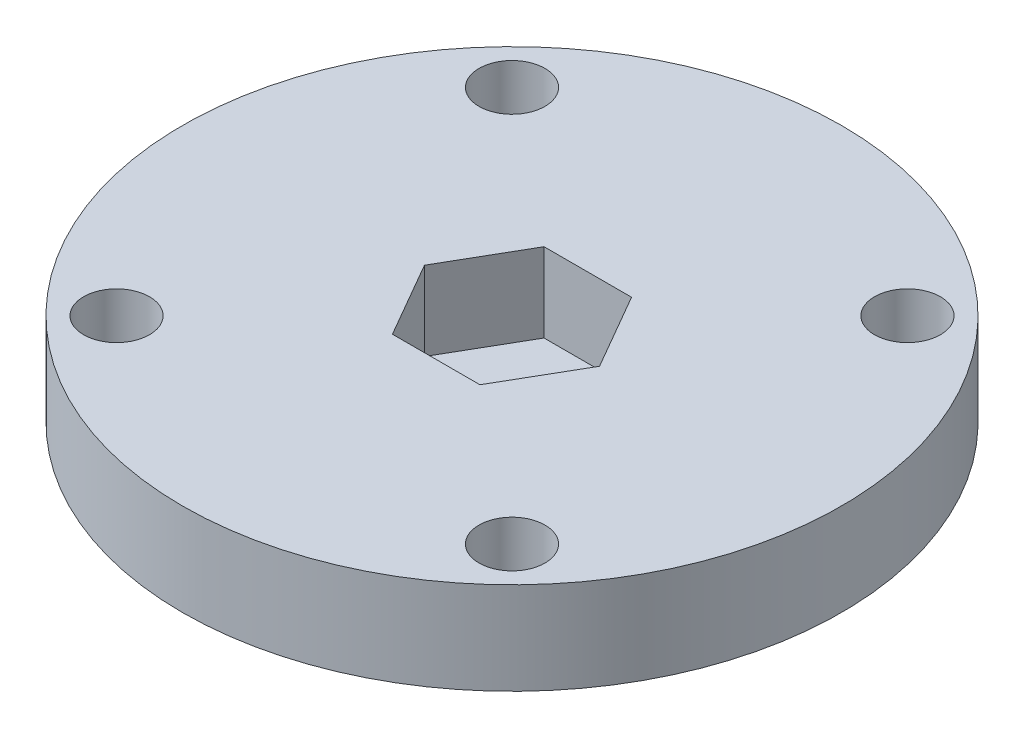
SolidWorks part; units mm, degrees
ref_plane "Front Plane" through (0, 0, 0) normal (0, 0, 1) x (1, 0, 0)
ref_plane "Top Plane" through (0, 0, 0) normal (0, 1, 0) x (1, 0, 0)
ref_plane "Right Plane" through (0, 0, 0) normal (1, 0, 0) x (0, 0, -1)
sketch "Sketch1" plane through (0, 0, 0) normal (0, 1, 0) x (1, 0, 0)
  circle A0 centre (0, 0) radius 25
  dimension "D1" = 50
extrude "Boss-Extrude1" add sketch "Sketch1" along normal blind 5
sketch "Sketch2" plane through (0, 5, 0) normal (0, 1, 0) x (1, 0, 0)
  line L4 (-15, -15) -> (15, -15) construction
  line L5 (-15, -15) -> (-15, 15) construction
  line L6 (-15, 15) -> (15, 15) construction
  line L7 (15, -15) -> (15, 15) construction
  line L8 (-15, -15) -> (15, 15) construction
  line L9 (-15, 15) -> (15, -15) construction
  circle A0 centre (-15, 15) radius 2.5
  circle A1 centre (15, 15) radius 2.5
  circle A2 centre (15, -15) radius 2.5
  circle A3 centre (-15, -15) radius 2.5
  point P6 (0, 0)
  point P21 (0, 0)
  dimension "D3" = 5
  dimension "D1" = 30
  dimension "D4" = 4
extrude "Cut-Extrude1" cut sketch "Sketch2" against normal through all
sketch "Sketch7" plane through (0, 5, 0) normal (0, 1, 0) x (1, 0, 0)
  line L0 (0, 5.65) -> (0, -5.65) construction
  line L1 (3.262, -5.65) -> (-3.262, -5.65)
  line L2 (3.262, 5.65) -> (-3.262, 5.65)
  line L3 (-6.5241, 0) -> (-3.262, 5.65)
  line L4 (4.893, -2.825) -> (-4.893, 2.825) construction
  line L5 (3.262, -5.65) -> (6.5241, 0)
  line L6 (3.262, 5.65) -> (6.5241, 0)
  line L7 (-4.893, -2.825) -> (4.893, 2.825) construction
  line L8 (-6.5241, 0) -> (-3.262, -5.65)
  line L9 (-6.5241, 0) -> (6.5241, 0) construction
  point P3 (0, 0)
  point P6 (0, -5.65)
  point P12 (0, 5.65)
  point P27 (0, 0)
  dimension "D1" = 11.3
  dimension "D2" = 3
extrude "Cut-Extrude2" cut sketch "Sketch7" against normal blind 4
other "Move Face1" face at (0, 5, 0) offset 2 parameters "D1"=2
other "Move Face2" flip direction yes face at (4.893, 4, -2.825) face at (4.893, 4, 2.825) face at (0, 4, 5.65) face at (-4.893, 4, 2.825) face at (-4.893, 4, -2.825) face at (0, 4, -5.65) offset 0.1 parameters "D1"=0.1
